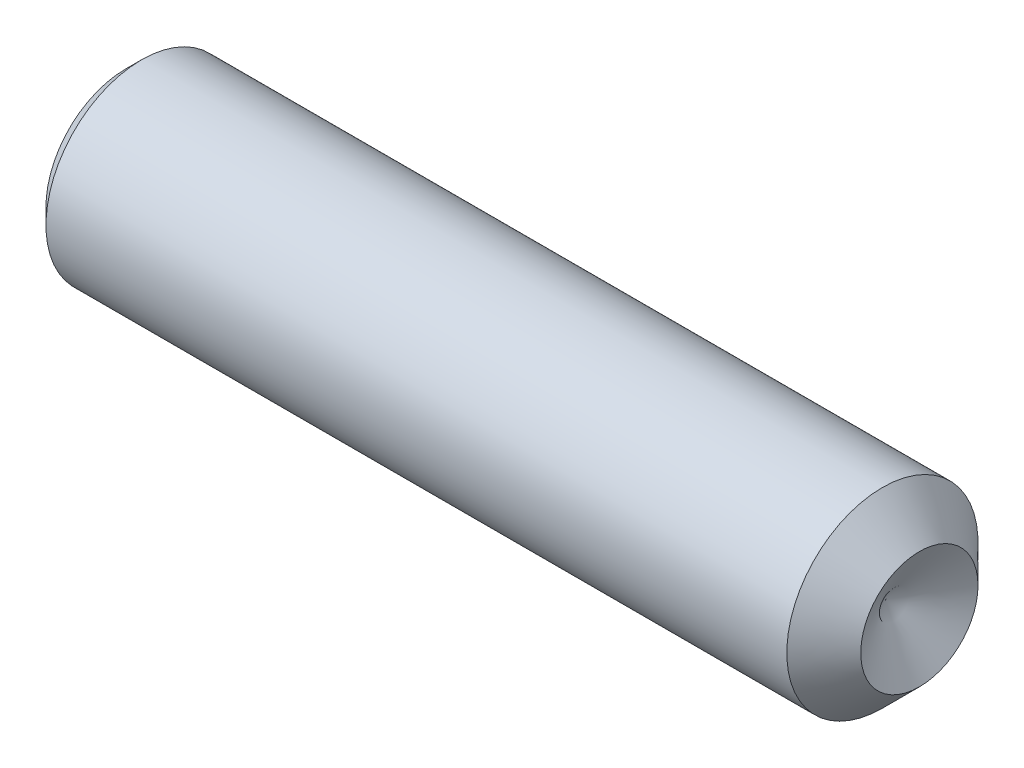
SolidWorks part; units mm, degrees
ref_plane "Front" through (0, 0, 0) normal (0, 0, 1) x (1, 0, 0)
ref_plane "Top" through (0, 0, 0) normal (0, 1, 0) x (1, 0, 0)
ref_plane "Right" through (0, 0, 0) normal (1, 0, 0) x (0, 0, -1)
sketch "Sketch1" plane through (0, 0, 0) normal (0, 0, 1) x (1, 0, 0)
  line L0 (0, 0) -> (0, 3)
  line L1 (0, 0) -> (25, 0)
  line L2 (0, 3) -> (25, 3)
  line L4 (25, 3) -> (25, 0)
  line L5 (25, 0) -> (0, 0) construction
  line L6 (25, 0) -> (0, 0) construction
  dimension "D1" = 6
  dimension "D2" = 25
revolve "Revolve1" add sketch "Sketch1" angle 360 about L6 reverse direction yes
cosmetic thread "Cosmetic Thread1" parameters "D2"=4.11
sketch "Sketch2" plane through (0, 0, 0) normal (0, 0, 1) x (1, 0, 0)
  line L0 (-1.1783, 0) -> (5.7343, 0) construction
  line L1 (2, 1.495) -> (2.8631, 0)
  line L2 (2, 1.495) -> (0, 1.495)
  line L3 (0, 3) -> (0, -3) construction
  line L5 (0, 1.495) -> (0, 0)
  line L6 (0, 0) -> (2.8631, 0)
  dimension "D1" = 60
  dimension "D2" = 2
  dimension "D3" = 2.99
revolve "Cut-Revolve1" cut sketch "Sketch2" angle 360 about L0 reverse direction yes
sketch "Sketch3" plane through (0, 0, 0) normal (-1, 0, 0) x (0, 0, 1)
  line L1 (0, 1.7321) -> (-1.5, 0.866)
  line L2 (-1.5, 0.866) -> (-1.5, -0.866)
  line L3 (-1.5, -0.866) -> (0, -1.7321)
  line L4 (0, -1.7321) -> (1.5, -0.866)
  line L5 (1.5, -0.866) -> (1.5, 0.866)
  line L6 (1.5, 0.866) -> (0, 1.7321)
  circle A0 centre (0, 0) radius 1.5 construction
  dimension "D1" = 3
extrude "Cut-Extrude1" cut sketch "Sketch3" against normal blind 2
sketch "Sketch4" plane through (0, 0, 0) normal (0, 0, 1) x (1, 0, 0)
  line L0 (-1.2565, 0) -> (6.9199, 0) construction
  line L1 (25, 1.995) -> (25, 0)
  line L2 (25, -3) -> (25, 3) construction
  line L3 (25, 0) -> (23.8482, 0)
  line L4 (23.8482, 0) -> (25, 1.995)
  dimension "D1" = 3.99
  dimension "D2" = 60
revolve "Cut-Revolve2" cut sketch "Sketch4" angle 360 about L0
chamfer "Chamfer1" distance 0.5 angle 45 1 edges at (0, -3, 0)
chamfer "Chamfer2" distance 1.25 angle 45 1 edges at (25, -3, 0)
